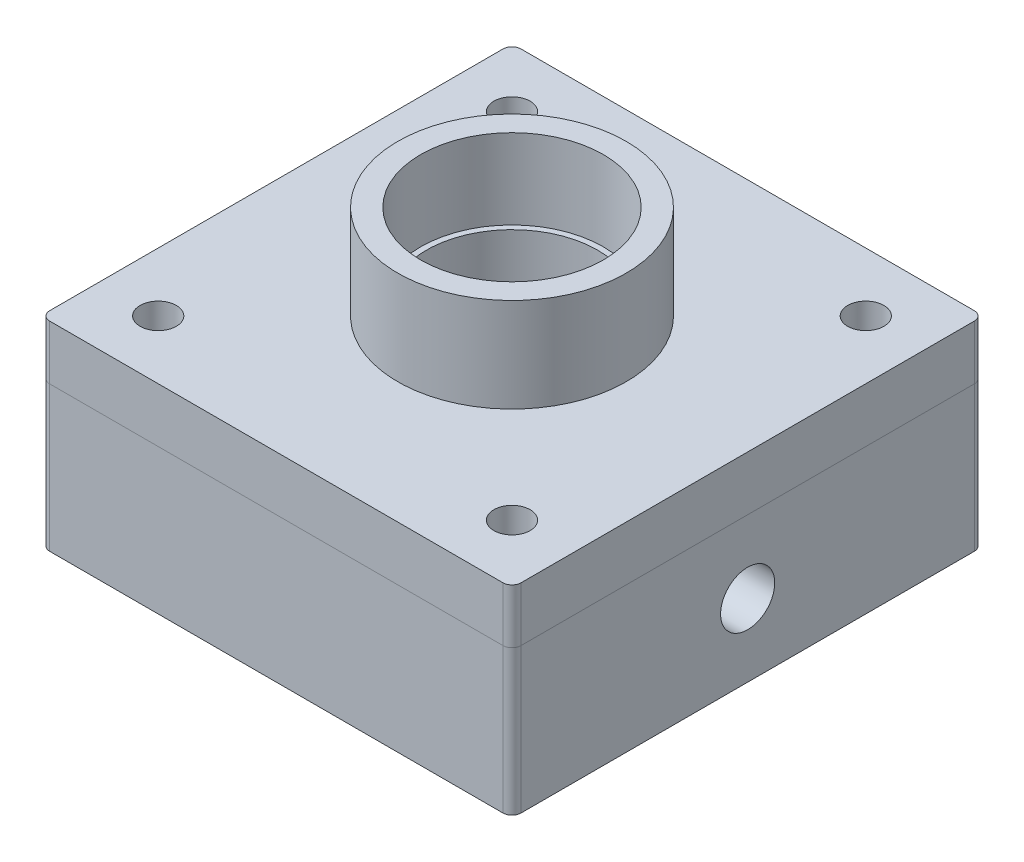
SolidWorks part; units mm, degrees
ref_plane "Front Plane" through (0, 0, 0) normal (0, 0, 1) x (1, 0, 0)
ref_plane "Top Plane" through (0, 0, 0) normal (0, 1, 0) x (1, 0, 0)
ref_plane "Right Plane" through (0, 0, 0) normal (1, 0, 0) x (0, 0, -1)
sketch "Sketch1" plane through (0, 0, 0) normal (0, 1, 0) x (1, 0, 0)
  line L1 (-82.55, 82.55) -> (82.55, 82.55)
  line L2 (-82.55, 82.55) -> (-82.55, -82.55)
  line L3 (-82.55, -82.55) -> (82.55, -82.55)
  line L4 (82.55, 82.55) -> (82.55, -82.55)
  line L5 (-82.55, 82.55) -> (82.55, -82.55) construction
  line L6 (-82.55, -82.55) -> (82.55, 82.55) construction
  circle A0 centre (0, 0) radius 30
  circle A1 centre (0, 0) radius 20
  circle A2 centre (0, 0) radius 32
  circle A3 centre (0, 0) radius 40
  circle A4 centre (0, 0) radius 87.63 construction
  circle A5 centre (-61.9638, 61.9638) radius 6.35
  circle A6 centre (61.9638, 61.9638) radius 6.35
  circle A7 centre (61.9638, -61.9638) radius 6.35
  circle A8 centre (-61.9638, -61.9638) radius 6.35
  point P0 (0, 0)
  point P23 (0, 0)
  dimension "D2" = 80
  dimension "D3" = 64
  dimension "D4" = 40
  dimension "D5" = 60
  dimension "D6" = 175.26
  dimension "D7" = 12.7
  dimension "D1" = 165.1
  dimension "D8" = 4
extrude "Boss-Extrude1" add sketch "Sketch1" along normal blind 102.8 contours A3 A2 region at (-38.8686, 0, 0)
extrude "Boss-Extrude2" add sketch "Sketch1<3>" along normal blind 74.8 contours A2 A0 region at (-31.0949, 0, 0)
sketch "Sketch1<3>" plane through (0, 0, 0) normal (0, 1, 0) x (1, 0, 0) same geometry as "Sketch1"
extrude "Boss-Extrude3" add sketch "Sketch1<4>" along normal blind 52.8 contours A0 A1 region at (-29.1515, 0, 0)
sketch "Sketch1<4>" plane through (0, 0, 0) normal (0, 1, 0) x (1, 0, 0) same geometry as "Sketch1"
extrude "Boss-Extrude4" add sketch "Sketch1<5>" along normal blind 50.8 contours L4 L1 L2 L3 A8 A7 A6 A5 A3 region at (0, 0, -80.2151)
sketch "Sketch1<5>" plane through (0, 0, 0) normal (0, 1, 0) x (1, 0, 0) same geometry as "Sketch1"
sketch "Sketch2" plane through (0, 0, 0) normal (0, -1, 0) x (1, 0, 0)
  circle A0 centre (0, 0) radius 69.85
  circle A1 centre (0, 0) radius 76.2
  dimension "D1" = 139.7
  dimension "D2" = 152.4
extrude "Cut-Extrude1" cut sketch "Sketch2" against normal blind 8
hole_wizard "Ø1.0mm Dowel Hole1" positions "Sketch5" profile "Sketch6" hole size "Ø1.0" standard "ANSI Metric"
sketch "Sketch5" plane through (82.55, 0, 0) normal (1, 0, 0) x (0, 0, -1)
  line L0 (82.55, 0) -> (-82.55, 0) construction
  point P0 (0, 25.4)
  dimension "D1" = 25.4
sketch "Sketch6" plane through (82.55, 25.4, 0) normal (0, 1, 0) x (0, 0, -1)
  line L0 (0, 0) -> (0, 52.7162)
  line L1 (0, 52.7162) -> (9.485, 47.24)
  line L2 (9.485, 47.24) -> (9.485, 0)
  line L5 (9.485, 0) -> (0, 0)
  line L10 (0, 52.7162) -> (-9.485, 47.24) construction
  line L11 (0, -6.35) -> (0, 107.95) construction
  dimension "Hole Dia." = 18.97
  dimension "Hole Depth" = 47.24
  dimension "Drill Angle" = 120
cosmetic thread "Cosmetic Thread1" parameters "D1"=41.91, "D2"=22
hole_wizard "Ø1.0mm Dowel Hole3" positions "Sketch9" profile "Sketch10" hole size "Ø1.0" standard "ANSI Metric" end condition up to next
sketch "Sketch9" plane through (0, 0, 0) normal (0, -1, 0) x (-1, 0, 0)
  line L0 (-82.55, 82.55) -> (-82.55, -82.55) construction
  point P0 (-50.55, 0)
  dimension "D1" = 32
sketch "Sketch10" plane through (50.55, 0, 0) normal (1, 0, 0) x (0, 0, -1)
  line L0 (0, 0) -> (0, 15.915)
  line L1 (0, 15.915) -> (6.35, 15.915)
  line L2 (6.35, 15.915) -> (6.35, 0)
  line L5 (6.35, 0) -> (0, 0)
  line L11 (0, -6.35) -> (0, 107.95) construction
  dimension "Thru Hole Dia." = 12.7
  dimension "Thru Hole Depth" = 15.915
sketch "Sketch12" plane through (0, 50.8, 0) normal (0, 1, 0) x (1, 0, 0)
  line L4 (82.55, -82.55) -> (82.55, 82.55)
  line L5 (82.55, 82.55) -> (-82.55, 82.55)
  line L6 (-82.55, 82.55) -> (-82.55, -82.55)
  line L7 (-82.55, -82.55) -> (82.55, -82.55)
  line L8 (82.55, -82.55) -> (82.55, 82.55)
  line L9 (82.55, 82.55) -> (-82.55, 82.55)
  line L10 (-82.55, 82.55) -> (-82.55, -82.55)
  line L11 (-82.55, -82.55) -> (82.55, -82.55)
  circle A0 centre (0, 0) radius 40 construction
  circle A1 centre (-61.9638, -61.9638) radius 6.35 construction
  circle A2 centre (-61.9638, 61.9638) radius 6.35 construction
  circle A3 centre (61.9638, 61.9638) radius 6.35 construction
  circle A4 centre (61.9638, -61.9638) radius 6.35 construction
  circle A5 centre (0, 0) radius 40
  circle A6 centre (-61.9638, -61.9638) radius 6.35
  circle A7 centre (-61.9638, 61.9638) radius 6.35
  circle A8 centre (61.9638, 61.9638) radius 6.35
  circle A9 centre (61.9638, -61.9638) radius 6.35
  dimension "D1" = 0
extrude "Boss-Extrude5" add sketch "Sketch12" along normal blind 19.05 separate body
fillet "Fillet3" radius 3.175 4 edges at (-82.55, 25.4, 82.55) (82.55, 25.4, 82.55) (-82.55, 25.4, -82.55) (82.55, 25.4, -82.55)
fillet "Fillet4" radius 3.175 4 edges at (-82.55, 60.325, -82.55) (82.55, 60.325, -82.55) (82.55, 60.325, 82.55) (-82.55, 60.325, 82.55)
